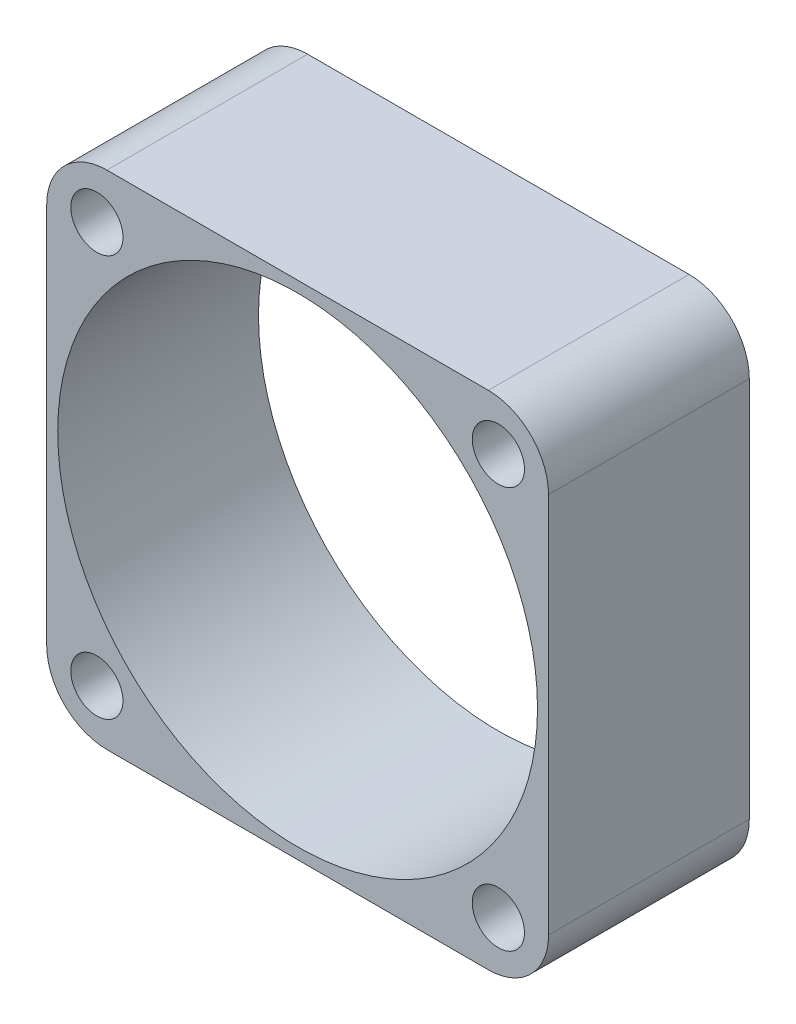
SolidWorks part; units mm, degrees
ref_plane "Plano frontal" through (0, 0, 0) normal (0, 0, 1) x (1, 0, 0)
ref_plane "Plano superior" through (0, 0, 0) normal (0, 1, 0) x (1, 0, 0)
ref_plane "Plano direito" through (0, 0, 0) normal (1, 0, 0) x (0, 0, -1)
sketch "Sketch1" plane through (0, 0, 0) normal (0, 0, 1) x (1, 0, 0)
  line L1 (-12.8242, -87.6141) -> (-37.8242, -87.6141)
  line L2 (-12.8242, -87.6141) -> (-12.8242, -62.6141)
  line L3 (-12.8242, -62.6141) -> (-37.8242, -62.6141)
  line L4 (-37.8242, -87.6141) -> (-37.8242, -62.6141)
  dimension "D1" = 25
  dimension "D2" = 25
extrude "Boss-Extrude1" add sketch "Sketch1" along normal blind 10
fillet "Fillet1" radius 3 4 edges at (-12.8242, -87.6141, 5) (-12.8242, -62.6141, 5) (-37.8242, -62.6141, 5) (-37.8242, -87.6141, 5)
sketch "Sketch2" plane through (0, 0, 10) normal (0, 0, 1) x (1, 0, 0)
  line L0 (-25.3242, -65.1141) -> (-25.3242, -85.1141) construction
  line L1 (-35.3242, -65.1141) -> (-15.3242, -65.1141) construction
  line L2 (-35.3242, -65.1141) -> (-35.3242, -85.1141) construction
  line L3 (-35.3242, -85.1141) -> (-15.3242, -85.1141) construction
  line L4 (-15.3242, -65.1141) -> (-15.3242, -85.1141) construction
  line L5 (-35.3242, -75.1141) -> (-15.3242, -75.1141) construction
  line L6 (-25.3242, -62.6141) -> (-25.3242, -87.5132) construction
  line L7 (-15.8242, -62.6141) -> (-34.8242, -62.6141) construction
  line L8 (-12.8242, -75.1141) -> (-37.8242, -75.1141) construction
  line L9 (-12.8242, -84.6141) -> (-12.8242, -65.6141) construction
  line L10 (-37.8242, -65.6141) -> (-37.8242, -84.6141) construction
  circle A0 centre (-35.3242, -65.1141) radius 1.3
  circle A1 centre (-15.3242, -65.1141) radius 1.3
  circle A2 centre (-15.3242, -85.1141) radius 1.3
  circle A3 centre (-35.3242, -85.1141) radius 1.3
  point P22 (-25.3242, -75.1141)
  point P23 (-25.3242, -75.0636)
  dimension "D3" = 2.6
  dimension "D4" = 2.6
  dimension "D5" = 2.6
  dimension "D6" = 2.6
  dimension "D1" = 20
  dimension "D2" = 20
extrude "Cut-Extrude1" cut sketch "Sketch2" against normal blind 10 contours A2 | A1 | A0 | A3 region at (-35.3242, -65.1141, 10) region at (-15.3242, -65.1141, 10) region at (-15.3242, -85.1141, 10)
sketch "Sketch3" plane through (0, 0, 10) normal (0, 0, 1) x (1, 0, 0)
  circle A0 centre (-25.3242, -75.1141) radius 11.95
  dimension "D1" = 23.9
extrude "Cut-Extrude2" cut sketch "Sketch3" against normal blind 10
